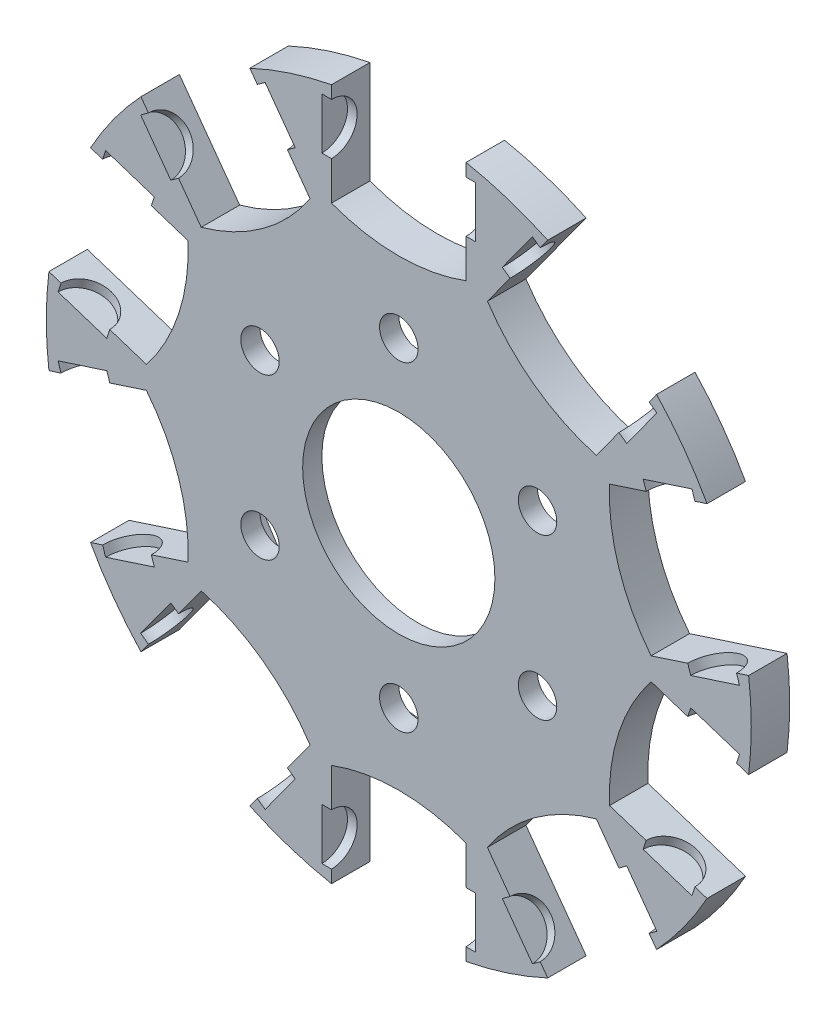
SolidWorks part; units mm, degrees
ref_plane "Front Plane" through (0, 0, 0) normal (0, 0, 1) x (1, 0, 0)
ref_plane "Top Plane" through (0, 0, 0) normal (0, 1, 0) x (1, 0, 0)
ref_plane "Right Plane" through (0, 0, 0) normal (1, 0, 0) x (0, 0, -1)
sketch "Sketch2" plane through (0, 0, 0) normal (0, 0, 1) x (1, 0, 0)
  line L0 (0, -2.3056) -> (0, 37.2834) construction
  line L1 (-5.25, 28.5556) -> (5.25, 28.5556) construction
  line L2 (-5.25, 26.9942) -> (-5.25, 18.9942)
  line L3 (5.25, 26.9942) -> (5.25, 18.9942)
  line L4 (11.6195, 24.9246) -> (6.9172, 18.4525)
  line L5 (20.1141, 18.7529) -> (15.4119, 12.2808)
  line L6 (24.0507, 13.3347) -> (16.4422, 10.8626)
  line L7 (27.2954, 3.3486) -> (19.6869, 0.8765)
  line L8 (27.2954, -3.3486) -> (19.6869, -0.8765)
  line L9 (24.0507, -13.3347) -> (16.4422, -10.8626)
  line L10 (20.1141, -18.7529) -> (15.4119, -12.2808)
  line L11 (11.6195, -24.9246) -> (6.9172, -18.4525)
  line L12 (5.25, -26.9942) -> (5.25, -18.9942)
  line L13 (-5.25, -26.9942) -> (-5.25, -18.9942)
  line L14 (-11.6195, -24.9246) -> (-6.9172, -18.4525)
  line L15 (-20.1141, -18.7529) -> (-15.4119, -12.2808)
  line L16 (-24.0507, -13.3347) -> (-16.4422, -10.8626)
  line L17 (-27.2954, -3.3486) -> (-19.6869, -0.8765)
  line L18 (-27.2954, 3.3486) -> (-19.6869, 0.8765)
  line L19 (-24.0507, 13.3347) -> (-16.4422, 10.8626)
  line L20 (-20.1141, 18.7529) -> (-15.4119, 12.2808)
  line L21 (-11.6195, 24.9246) -> (-6.9172, 18.4525)
  circle A0 centre (0, 0) radius 27.5
  circle A1 centre (0, 0) radius 12.5 construction
  circle A2 centre (0, 0) radius 15.5 construction
  circle A3 centre (-10.8253, 6.25) radius 1.5
  circle A4 centre (0, 12.5) radius 1.5
  circle A5 centre (10.8253, 6.25) radius 1.5
  circle A6 centre (10.8253, -6.25) radius 1.5
  circle A7 centre (0, -12.5) radius 1.5
  circle A8 centre (-10.8253, -6.25) radius 1.5
  arc A9 (-5.25, 18.9942) -> (5.25, 18.9942) centre (0, 33.0455) ccw
  arc A10 (6.9172, 18.4525) -> (15.4119, 12.2808) centre (19.4236, 26.7343) ccw
  arc A11 (16.4422, 10.8626) -> (19.6869, 0.8765) centre (31.4281, 10.2116) ccw
  arc A12 (19.6869, -0.8765) -> (16.4422, -10.8626) centre (31.4281, -10.2116) ccw
  arc A13 (15.4119, -12.2808) -> (6.9172, -18.4525) centre (19.4236, -26.7343) ccw
  arc A14 (5.25, -18.9942) -> (-5.25, -18.9942) centre (0, -33.0455) ccw
  arc A15 (-6.9172, -18.4525) -> (-15.4119, -12.2808) centre (-19.4236, -26.7343) ccw
  arc A16 (-16.4422, -10.8626) -> (-19.6869, -0.8765) centre (-31.4281, -10.2116) ccw
  arc A17 (-19.6869, 0.8765) -> (-16.4422, 10.8626) centre (-31.4281, 10.2116) ccw
  arc A18 (-15.4119, 12.2808) -> (-6.9172, 18.4525) centre (-19.4236, 26.7343) ccw
  circle A19 centre (0, 0) radius 7.5
  circle A20 centre (0, 0) radius 15.5
  point P9 (0, 28.5556)
  point P25 (0, 0)
  point P75 (0, 0)
  point P78 (2.7699, -0.9)
  point P79 (0, 0)
  point P80 (0, 0)
  point P82 (0, 0)
  dimension "D1" = 55
  dimension "D2" = 10.5
  dimension "37" = 25
  dimension "D3" = 10
  dimension "35" = 31
  dimension "D4" = 3
  dimension "D8" = 15
  dimension "D7" = 15
  dimension "D6" = 8
  dimension "D5" = 6
extrude "Boss-Extrude2" add sketch "Sketch2" along normal blind 3 contours A0 L3 A9 L2 A20 | A20 A3 A4 A5 A6 A7 A8 A19 region at (-6.0207, 22.9942, 0) region at (-15.0616, 0, 0)
extrude "Boss-Extrude3" add sketch "Sketch2<4>" along normal blind 3 contours A20 A8 A1 A3 A4 A5 A6 A7 region at (-15.0616, 0, 0)
sketch "Sketch2<4>" plane through (0, 0, 0) normal (0, 0, 1) x (1, 0, 0) same geometry as "Sketch2"
sketch "Sketch3" plane through (0, 0, 3) normal (0, 0, 1) x (1, 0, 0)
  line L0 (0, 28.1882) -> (0, 8.7236) construction
  line L1 (-4.625, 27.1083) -> (4.625, 27.1083) construction
  line L3 (-6.683, 24) -> (6.8867, 24) construction
  line L4 (-6, 26) -> (6, 26)
  line L5 (6, 26) -> (6, 24)
  line L6 (-6, 26) -> (-6, 24)
  line L7 (6, 24) -> (-6, 24)
  point P15 (0, 26)
  dimension "D1" = 24
  dimension "D2" = 12
  dimension "D3" = 2
  dimension "D4" = 2
revolve "Cut-Revolve1" cut sketch "Sketch3" angle 360 about L7
pattern_circular "CirPattern1" count 10 over 360 about axis through (0, 0, 0) along (0, 0, 1) of "Cut-Revolve1"
sketch "Sketch4" plane through (0, 0, 3) normal (0, 0, 1) x (1, 0, 0)
sketch "Sketch5" plane through (0, 0, 0) normal (0, 0, -1) x (-1, 0, 0)
  circle A0 centre (0, 0) radius 15.5
  dimension "D1" = 31
extrude "Cut-Extrude2" cut sketch "Sketch5" against normal blind 1.5
